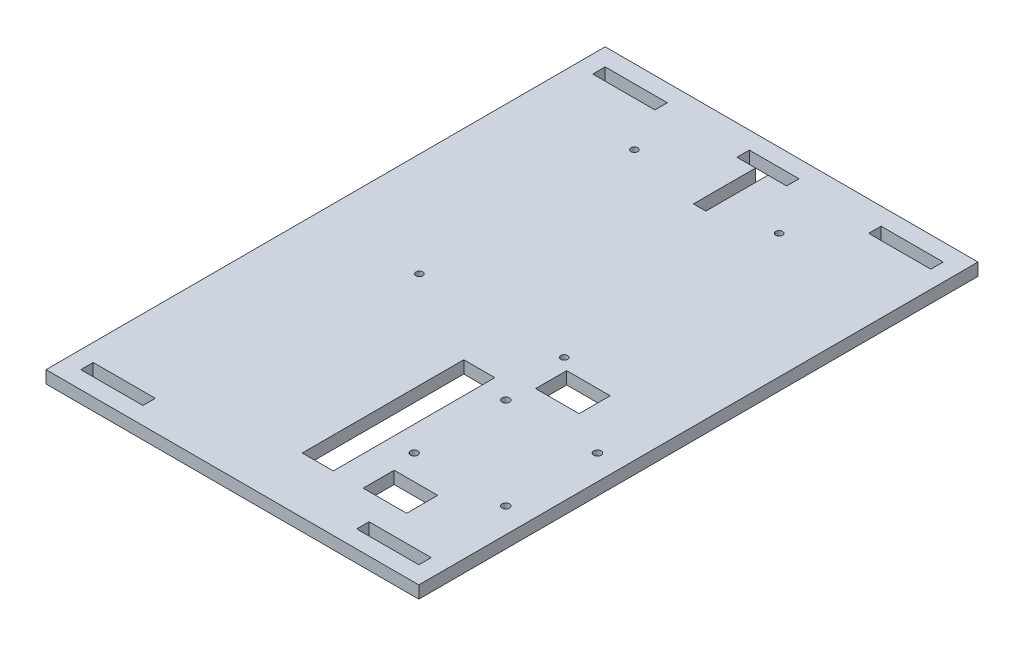
SolidWorks part; units mm, degrees
ref_plane "Front Plane" through (0, 0, 0) normal (0, 0, 1) x (1, 0, 0)
ref_plane "Top Plane" through (0, 0, 0) normal (0, 1, 0) x (1, 0, 0)
ref_plane "Right Plane" through (0, 0, 0) normal (1, 0, 0) x (0, 0, -1)
sketch "Sketch1" plane through (0, 0, 0) normal (0, 1, 0) x (1, 0, 0)
  line L1 (-75, 112.5) -> (75, 112.5)
  line L2 (-75, 112.5) -> (-75, -112.5)
  line L3 (-75, -112.5) -> (75, -112.5)
  line L4 (75, 112.5) -> (75, -112.5)
  point P4 (0, 112.5)
  point P6 (-75, 0)
  dimension "D1" = 150
  dimension "D2" = 225
extrude "Boss-Extrude1" add sketch "Sketch1" along normal blind 5
sketch "Sketch2" plane through (0, 5, 0) normal (0, 1, 0) x (1, 0, 0)
  line L0 (-33.25, 82.5) -> (25, 82.5) construction
  line L1 (-33.25, 82.5) -> (-33.25, -4) construction
  circle A0 centre (-33.25, 82.5) radius 1.375
  circle A1 centre (25, 82.5) radius 1.375
  circle A2 centre (25, -4) radius 1.375
  circle A3 centre (-33.25, -4) radius 1.375
  dimension "D3" = 2.75
  dimension "D1" = 58.25
  dimension "D2" = 86.5
  dimension "D4" = 30
  dimension "D5" = 50
sketch "Sketch3" plane through (0, 5, 0) normal (0, 1, 0) x (1, 0, 0)
  line L0 (28.1, -30.6) -> (28.1, -67.5) construction
  line L1 (28.1, -30.6) -> (65, -30.6) construction
  circle A0 centre (28.1, -30.6) radius 1.5
  circle A1 centre (65, -30.6) radius 1.5
  circle A2 centre (65, -67.5) radius 1.5
  circle A3 centre (28.1, -67.5) radius 1.5
  dimension "D1" = 3
  dimension "D2" = 36.9
  dimension "D3" = 45
  dimension "D4" = 10
sketch "Sketch6" plane through (0, 5, 0) normal (0, 1, 0) x (1, 0, 0)
  line L10 (-10, 105.5) -> (10, 105.5)
  line L11 (-10, 105.5) -> (-10, 100.5)
  line L12 (-10, 100.5) -> (10, 100.5)
  line L13 (10, 105.5) -> (10, 100.5)
  point P4 (0, 105.5)
  dimension "D1" = 20
  dimension "D2" = 7
  dimension "D3" = 5
extrude "Cut-Extrude1" cut sketch "Sketch2" against normal through all
extrude "Cut-Extrude2" cut sketch "Sketch3" against normal through all
extrude "Cut-Extrude3" cut sketch "Sketch6" against normal through all
sketch "Sketch9" plane through (0, 5, 0) normal (0, 1, 0) x (1, 0, 0)
  line L1 (5.6, -90) -> (18.1, -90)
  line L2 (5.6, -90) -> (5.6, -25)
  line L3 (5.6, -25) -> (18.1, -25)
  line L4 (18.1, -90) -> (18.1, -25)
  line L5 (30.1, -8.1) -> (47.6, -8.1)
  line L6 (30.1, -8.1) -> (30.1, -20.6)
  line L7 (30.1, -20.6) -> (47.6, -20.6)
  line L8 (47.6, -8.1) -> (47.6, -20.6)
  line L9 (30.1, -77.5) -> (47.6, -77.5)
  line L10 (30.1, -77.5) -> (30.1, -90)
  line L11 (30.1, -90) -> (47.6, -90)
  line L12 (47.6, -77.5) -> (47.6, -90)
  circle A0 centre (28.1, -30.6) radius 1.5 construction
  circle A1 centre (28.1, -67.5) radius 1.5 construction
  dimension "D1" = 2
  dimension "D5" = 10
  dimension "D2" = 12.5
  dimension "D3" = 17.5
  dimension "D4" = 10
  dimension "D6" = 10
  dimension "D7" = 12.5
  dimension "D8" = 65
extrude "Cut-Extrude4" cut sketch "Sketch9" against normal up to surface (5 mm away) up to face at (0, 0, -103)
sketch "Sketch10" plane through (0, 5, 0) normal (0, 1, 0) x (1, 0, 0)
  line L0 (0, 0) -> (-75, 0) construction
  line L1 (-68, -105.5) -> (-43, -105.5)
  line L2 (-68, -105.5) -> (-68, -100.5)
  line L3 (-68, -100.5) -> (-43, -100.5)
  line L4 (-43, -105.5) -> (-43, -100.5)
  line L9 (-75, 112.5) -> (-75, -112.5) construction
  line L10 (0, 0) -> (0, -112.5) construction
  line L11 (-75, -112.5) -> (75, -112.5) construction
  line L12 (-68, 100.5) -> (-43, 100.5)
  line L13 (-43, 105.5) -> (-43, 100.5)
  line L14 (-68, 105.5) -> (-43, 105.5)
  line L15 (-68, 105.5) -> (-68, 100.5)
  line L16 (68, -100.5) -> (43, -100.5)
  line L17 (43, -105.5) -> (43, -100.5)
  line L18 (68, -105.5) -> (43, -105.5)
  line L19 (68, -105.5) -> (68, -100.5)
  line L20 (68, 105.5) -> (68, 100.5)
  line L21 (68, 105.5) -> (43, 105.5)
  line L22 (43, 105.5) -> (43, 100.5)
  line L23 (68, 100.5) -> (43, 100.5)
  dimension "D1" = 7
  dimension "D2" = 7
  dimension "D3" = 5
  dimension "D4" = 25
extrude "Cut-Extrude5" cut sketch "Sketch10" against normal up to surface (5 mm away) up to face at (11.85, 0, 57.5)
sketch "Sketch11" plane through (0, 5, 0) normal (0, 1, 0) x (1, 0, 0)
  line L0 (-10, 100.5) -> (10, 100.5) construction
  line L1 (-2.5, 100.5) -> (2.5, 100.5)
  line L2 (2.5, 100.5) -> (2.5, 75.5)
  line L3 (2.5, 75.5) -> (-2.5, 75.5)
  line L4 (-2.5, 75.5) -> (-2.5, 100.5)
  point P6 (0, 100.5)
  point P9 (0, 100.5)
  dimension "D1" = 5
  dimension "D2" = 25
extrude "Cut-Extrude6" cut sketch "Sketch11" against normal up to surface (5 mm away) up to face at (-55.5, 0, -103)
